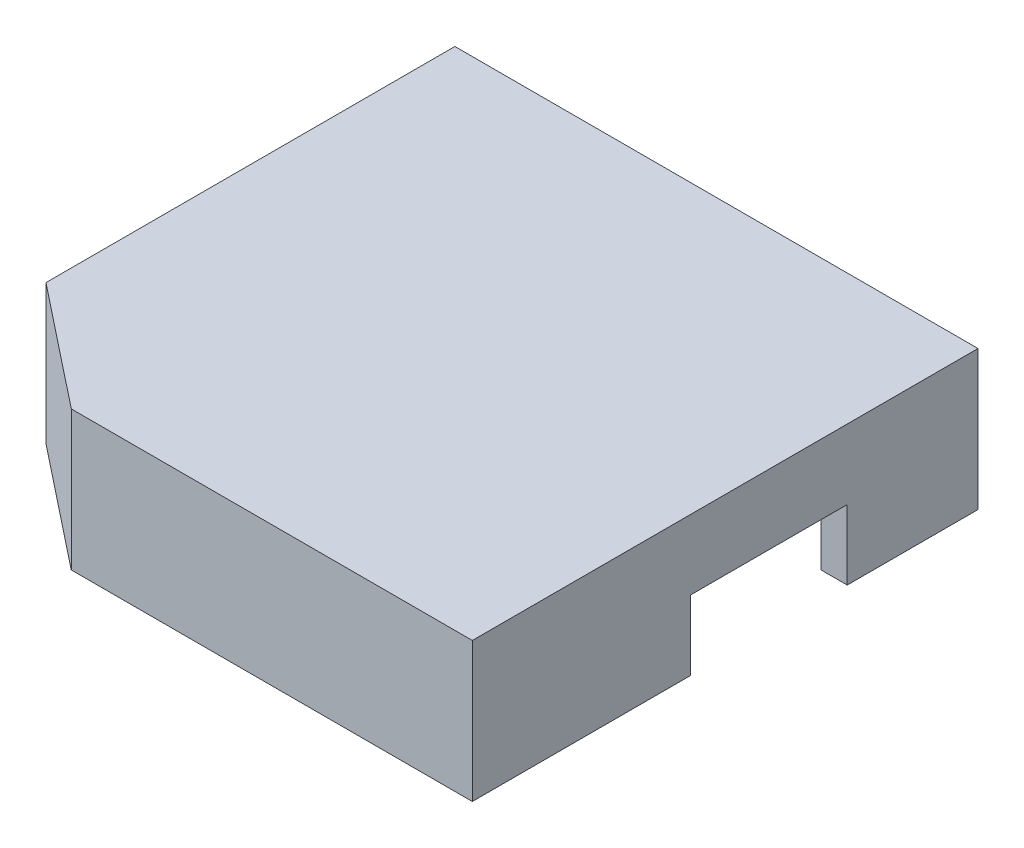
SolidWorks part; units mm, degrees
ref_plane "Front Plane" through (0, 0, 0) normal (0, 0, 1) x (1, 0, 0)
ref_plane "Top Plane" through (0, 0, 0) normal (0, 1, 0) x (1, 0, 0)
ref_plane "Right Plane" through (0, 0, 0) normal (1, 0, 0) x (0, 0, -1)
sketch "Sketch1" plane through (0, 0, 0) normal (0, 1, 0) x (1, 0, 0)
  line L1 (-29.2366, 0.9308) -> (0.7634, 0.9308)
  line L2 (-29.2366, 0.9308) -> (-29.2366, -28.0692)
  line L3 (-29.2366, -28.0692) -> (0.7634, -28.0692)
  line L4 (0.7634, 0.9308) -> (0.7634, -28.0692)
  dimension "D1" = 30
  dimension "D2" = 29
extrude "Boss-Extrude1" add sketch "Sketch1" along normal blind 8
sketch "Sketch2" plane through (0, 8, 0) normal (0, 1, 0) x (1, 0, 0)
  line L0 (-29.2366, 0.9308) -> (-29.2366, -28.0692) construction
  line L1 (-26.2366, -2.0692) -> (-2.2366, -2.0692)
  line L2 (-26.2366, -2.0692) -> (-26.2366, -10.0692)
  line L3 (-26.2366, -10.0692) -> (-2.2366, -10.0692)
  line L4 (-2.2366, -2.0692) -> (-2.2366, -10.0692)
  line L5 (-26.2366, -13.0692) -> (-2.2366, -13.0692)
  line L6 (-26.2366, -13.0692) -> (-26.2366, -21.0692)
  line L7 (-26.2366, -21.0692) -> (-2.2366, -21.0692)
  line L8 (-2.2366, -13.0692) -> (-2.2366, -21.0692)
  line L9 (0.7634, -28.0692) -> (0.7634, 0.9308) construction
  line L10 (0.7634, 0.9308) -> (-29.2366, 0.9308) construction
  dimension "D1" = 3
  dimension "D2" = 3
  dimension "D3" = 3
  dimension "D4" = 3
  dimension "D5" = 8
  dimension "D6" = 3
extrude "Cut-Extrude1" cut sketch "Sketch2" against normal blind 8
sketch "Sketch3" plane through (0, 8, 0) normal (0, 1, 0) x (1, 0, 0)
  line L0 (-29.2366, -22.5191) -> (-22.2366, -28.0692)
  line L1 (-29.2366, 0.9308) -> (-29.2366, -28.0692) construction
  line L2 (-29.2366, -28.0692) -> (0.7634, -28.0692) construction
  line L3 (-22.2366, -28.0692) -> (-29.2366, -28.0692)
  line L4 (-29.2366, -28.0692) -> (-29.2366, -22.5191)
  dimension "D1" = 3
  dimension "D2" = 7
extrude "Cut-Extrude2" cut sketch "Sketch3" against normal blind 8
sketch "Sketch4" plane through (0, 0, 0) normal (0, -1, 0) x (1, 0, 0)
  line L0 (-0.7366, 0.5692) -> (-27.7366, 0.5692)
  line L1 (-27.7366, 0.5692) -> (-27.7366, 21.7942)
  line L2 (-27.7366, 21.7942) -> (-21.7141, 26.5692)
  line L3 (-21.7141, 26.5692) -> (-0.7366, 26.5692)
  line L4 (-0.7366, 0.5692) -> (-0.7366, 26.5692)
  line L5 (0.7634, 28.0692) -> (0.7634, -0.9308) construction
  line L6 (-22.2366, 28.0692) -> (0.7634, 28.0692) construction
  line L7 (-22.2366, 28.0692) -> (-29.2366, 22.5191) construction
  line L8 (-29.2366, -0.9308) -> (-29.2366, 22.5191) construction
  line L9 (0.7634, -0.9308) -> (-29.2366, -0.9308) construction
  point P15 (-25.7366, 25.2942)
  dimension "D1" = 1.5
  dimension "D2" = 1.5
  dimension "D3" = 1.5
  dimension "D4" = 1.5
  dimension "D5" = 1.5
extrude "Cut-Extrude3" cut sketch "Sketch4" against normal blind 5
sketch "Sketch5" plane through (-29.2366, 0, 0) normal (-1, 0, 0) x (0, 0, 1)
  line L0 (-0.9308, 0) -> (22.5191, 0) construction
  line L1 (6.5692, 0) -> (15.5692, 0)
  line L2 (6.5692, 0) -> (6.5692, 4)
  line L3 (6.5692, 4) -> (15.5692, 4)
  line L4 (15.5692, 0) -> (15.5692, 4)
  line L5 (-0.9308, 8) -> (-0.9308, 0) construction
  dimension "D1" = 9
  dimension "D2" = 4
  dimension "D3" = 7.5
extrude "Cut-Extrude4" cut sketch "Sketch5" against normal blind 30
extrude "Boss-Extrude2" add sketch "Sketch2<2>" against normal blind 3
sketch "Sketch2<2>" plane through (0, 8, 0) normal (0, 1, 0) x (1, 0, 0) same geometry as "Sketch2"
